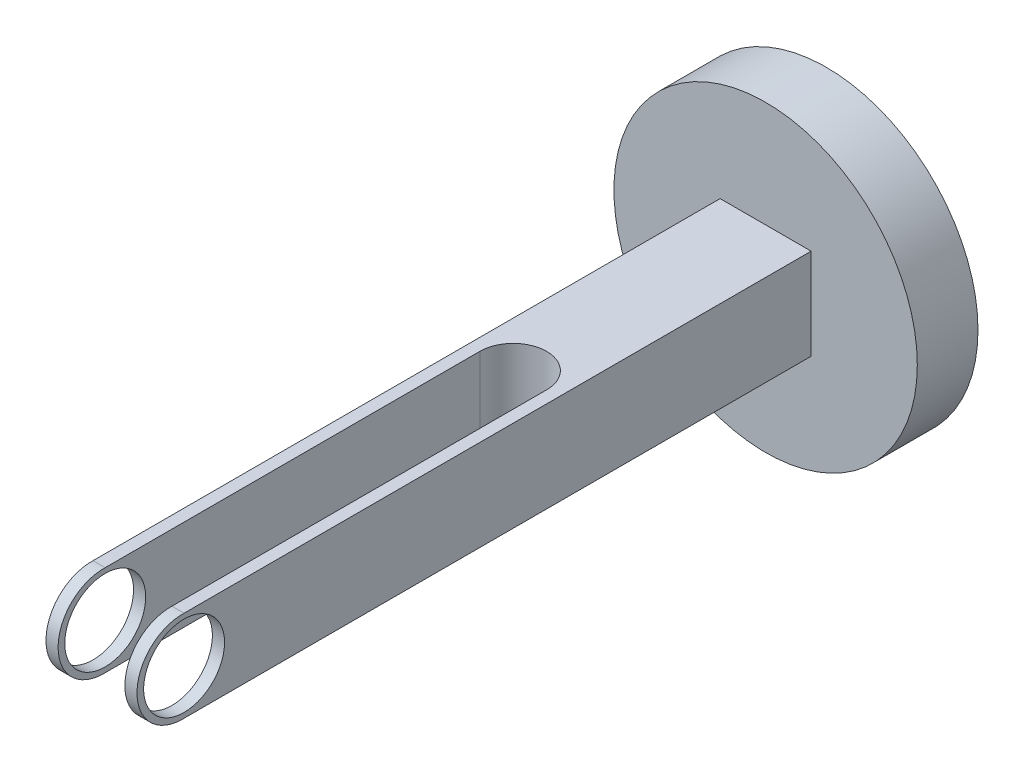
SolidWorks part; units mm, degrees
ref_plane "Front Plane" through (0, 0, 0) normal (0, 0, 1) x (1, 0, 0)
ref_plane "Top Plane" through (0, 0, 0) normal (0, 1, 0) x (1, 0, 0)
ref_plane "Right Plane" through (0, 0, 0) normal (1, 0, 0) x (0, 0, -1)
sketch "Sketch1" plane through (0, 0, 0) normal (0, 0, 1) x (1, 0, 0)
  circle A0 centre (0, 0) radius 75
  dimension "D1" = 150
extrude "Boss-Extrude1" add sketch "Sketch1" along normal blind 30
sketch "Sketch2" plane through (0, 0, 30) normal (0, 0, 1) x (1, 0, 0)
  line L1 (-22.5, -22.5) -> (22.5, -22.5)
  line L2 (-22.5, -22.5) -> (-22.5, 22.5)
  line L3 (-22.5, 22.5) -> (22.5, 22.5)
  line L4 (22.5, -22.5) -> (22.5, 22.5)
  line L5 (-22.5, -22.5) -> (22.5, 22.5) construction
  line L6 (-22.5, 22.5) -> (22.5, -22.5) construction
  point P0 (0, 0)
  dimension "D1" = 45
  dimension "D2" = 45
extrude "Boss-Extrude2" add sketch "Sketch2" along normal blind 335.79
sketch "Sketch3" plane through (22.5, 0, 0) normal (1, 0, 0) x (0, 0, -1)
  line L1 (-365.79, -22.5) -> (-365.79, 22.5) construction
  line L3 (-339.2145, 22.4448) -> (-418.3272, 27.998)
  line L4 (-418.3272, 27.998) -> (-417.7344, -27.0511)
  line L5 (-417.7344, -27.0511) -> (-340.79, -22.5)
  arc A0 (-339.2145, 22.4448) -> (-340.79, -22.5) centre (-340.79, 0) ccw
  dimension "D2" = 45
  dimension "D1" = 25
extrude "Cut-Extrude1" cut sketch "Sketch3" against normal blind 380
sketch "Sketch4" plane through (22.5, 0, 0) normal (1, 0, 0) x (0, 0, -1)
  line L0 (-340.0013, 22.5) -> (-340.0013, -22.5)
  line L1 (-340.79, -22.5) -> (-30, -22.5) construction
  circle A0 centre (-340.0013, 0) radius 20
  dimension "D1" = 40
extrude "Cut-Extrude2" cut sketch "Sketch4" against normal blind 380 contours L0 A0 | L0 A0 region at (22.5, 0, 331.513) region at (22.5, 0, 348.4896)
sketch "Sketch5" plane through (0, 22.5, 0) normal (0, 1, 0) x (1, 0, 0)
  line L0 (-16.0833, 185.4209) -> (16.9167, 185.4209)
  line L1 (-16.5, -154.792) -> (-16.5, -435.1609)
  line L2 (16.5, -154.792) -> (16.5, -435.1609)
  line L3 (-16.5, -435.1609) -> (16.5, -435.1609)
  line L4 (22.5, -340.0013) -> (22.5, -30) construction
  arc A0 (16.5, -154.792) -> (-16.5, -154.792) centre (0, -154.792) ccw
  point P1 (0.4167, -124.87)
  line M4 (-22.5, -340.0013) -> (22.5, -340.0013)
  dimension "D1" = 33
  dimension "D2" = 6
extrude "Cut-Extrude3" cut sketch "Sketch5" against normal blind 380 contours L2 A0 L1 M4 | L1 L3 L2 M4 region at (0, 22.5, 240.8829) region at (0, 22.5, 387.5811)
